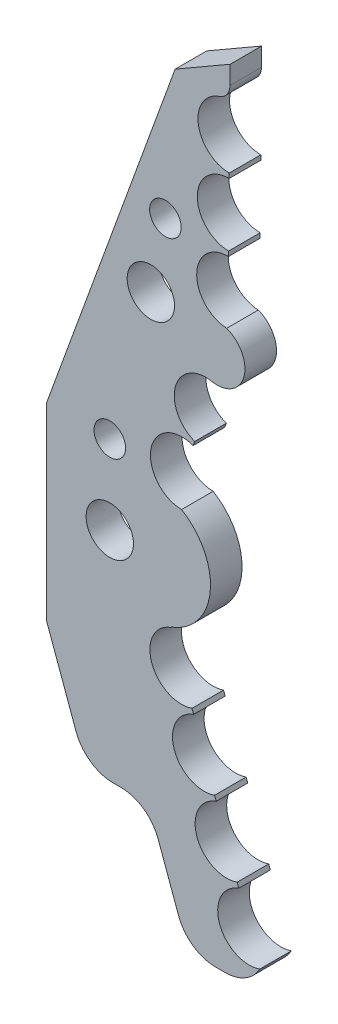
SolidWorks part; units mm, degrees
ref_plane "Plan de face" through (0, 0, 0) normal (0, 0, 1) x (1, 0, 0)
ref_plane "Plan de dessus" through (0, 0, 0) normal (0, 1, 0) x (1, 0, 0)
ref_plane "Plan de droite" through (0, 0, 0) normal (1, 0, 0) x (0, 0, -1)
sketch "Esquisse1" plane through (0, 0, 0) normal (0, 0, 1) x (1, 0, 0)
  line L0 (3.4499, -1.1105) -> (8.4499, -1.1105)
  line L2 (-5.5082, 12.5118) -> (-5.5082, 24.5118)
  line L3 (-5.5082, 24.5118) -> (2.632, 46.8768)
  line L4 (2.632, 46.8768) -> (6.1182, 48.8895)
  line L5 (6.1182, 48.8895) -> (5.962, 32.6355)
  line L6 (5.962, 32.6355) -> (1.1067, 19.6842)
  line L7 (1.1067, 19.6842) -> (8.4499, -1.1105)
  line L8 (3.4499, -1.1105) -> (0.9545, 5.7456)
  line L9 (0.9545, 5.7456) -> (-3.0455, 5.7456)
  line L10 (-3.0455, 5.7456) -> (-5.5082, 12.5118)
  circle A0 centre (6.0797, 44.8897) radius 2
  circle A1 centre (6.0384, 40.5897) radius 2
  circle A2 centre (5.9971, 36.2897) radius 2
  circle A3 centre (5.2893, 32.6355) radius 1.7659
  circle A4 centre (4.5771, 28.9414) radius 2
  circle A5 centre (3.0677, 24.9151) radius 2
  circle A6 centre (1.1067, 19.6842) radius 3.7665
  circle A7 centre (3.0346, 14.2246) radius 2
  circle A8 centre (4.4664, 10.1699) radius 2
  circle A9 centre (5.8982, 6.1153) radius 2
  circle A10 centre (7.33, 2.0607) radius 2
  point P31 (0, 0)
  point P32 (0, 0)
  dimension "D12" = 4
  dimension "D14" = 4
  dimension "D16" = 4
  dimension "D18" = 4
  dimension "D20" = 4
  dimension "D22" = 4
  dimension "D23" = 4
  dimension "D24" = 4
  dimension "D28" = 4
  dimension "D1" = 50
  dimension "D2" = 5
  dimension "D3" = 4
  dimension "D4" = 110
  dimension "D5" = 110
  dimension "D6" = 160
  dimension "D7" = 12
  dimension "D8" = 140
  dimension "D9" = 160
  dimension "D10" = 8
  dimension "D11" = 140
  dimension "D13" = 4
  dimension "D15" = 4.3
  dimension "D17" = 4.3
  dimension "D19" = 3.9452
  dimension "D21" = 4.3
  dimension "D25" = 5.79
  dimension "D26" = 4.3
  dimension "D27" = 4.3
  dimension "D29" = 4.3
extrude "Boss.-Extru.2" add sketch "Esquisse1" along normal blind 2 contours A10 L7 A9 A8 A7 A6 A5 L6 A4 A3 A2 L5 A1 A0 L4 L3 L2 L10 L9 L8 L0 | A5 A6 L7 L6 | L7 A6 A5 L6 | A4 A3 L6 L5 A2 | L6 A3 L5 region at (2.69, 2.4951, 0) region at (-0.1291, 19.6853, 0) region at (3.0398, 19.6496, 0) region at (4.8163, 32.7292, 0) region at (6.2953, 32.427, 0)
fillet "Congé1" radius 1 1 edges at (6.0989, 46.8896, 1)
sketch "Esquisse2" plane through (0, 0, 2) normal (0, 0, 1) x (1, 0, 0)
  line L0 (6.0192, 38.5898) -> (6.0163, 38.2896) construction
  line L3 (-5.5082, 24.5118) -> (2.632, 46.8768) construction
  line L4 (-5.5082, 12.5118) -> (-5.5082, 24.5118) construction
  circle A0 centre (2.017, 38.3768) radius 1
  circle A1 centre (1.0929, 33.8768) radius 1.5
  circle A2 centre (-1.5082, 19.5118) radius 1.5
  circle A3 centre (-1.5082, 24.5118) radius 1
  point P10 (0, 0)
  point P11 (0, 0)
  point P13 (-1.4542, 35.65)
  point P19 (-5.5082, 23.3734)
  point P22 (-5.5082, 23.4731)
  dimension "D1" = 2
  dimension "D4" = 3
  dimension "D7" = 2
  dimension "D8" = 3
  dimension "D2" = 4
  dimension "D3" = 8.5
  dimension "D5" = 13
  dimension "D6" = 3
  dimension "D9" = 0
  dimension "D10" = 4
  dimension "D11" = 4
  dimension "D12" = 5
extrude "Enlèv. mat.-Extru.1" cut sketch "Esquisse2" against normal through all
fillet "Congé2" radius 2.5 4 edges at (8.4499, -1.1105, 1) (3.4499, -1.1105, 1) (0.9545, 5.7456, 1) (-3.0455, 5.7456, 1)
